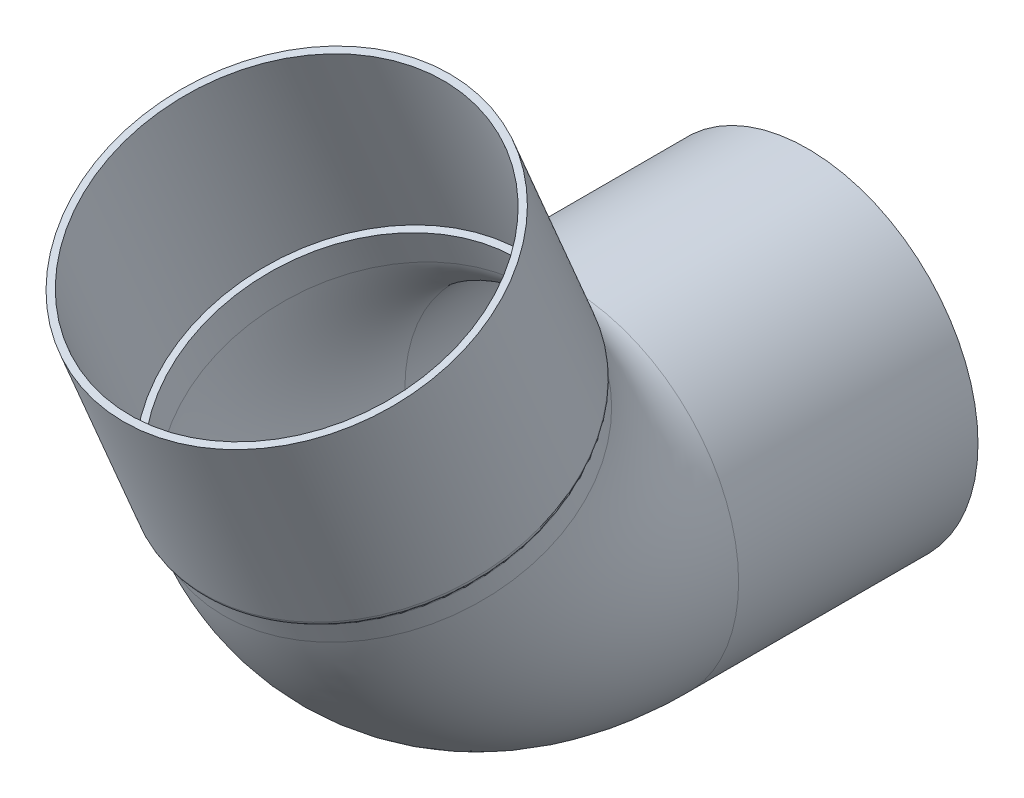
SolidWorks part; units mm, degrees
ref_plane "Plan de face" through (0, 0, 0) normal (0, 0, 1) x (1, 0, 0)
ref_plane "Plan de dessus" through (0, 0, 0) normal (0, 1, 0) x (1, 0, 0)
ref_plane "Plan de droite" through (0, 0, 0) normal (1, 0, 0) x (0, 0, -1)
sketch "Esquisse6" plane through (0, 0, 0) normal (0, 0, 1) x (1, 0, 0)
  circle A0 centre (0, 0) radius 25
sketch "Esquisse7" plane through (0, 0, 0) normal (1, 0, 0) x (0, 0, -1)
  line L0 (0, 0) -> (-35.1434, 0)
  line L1 (-62.7586, 18.2781) -> (-64.3775, 22.0921)
  arc A0 (-35.1434, 0) -> (-62.7586, 18.2781) centre (-35.1434, 30) cw
  point P6 (-55, 0)
  dimension "D4" = 30
  dimension "D1" = 24
  dimension "D2" = 55
  dimension "D3" = 67
sweep "Balayage-Mince2" add profiles "Esquisse6" path "Esquisse7" parameters "D1"=1
sketch "Esquisse8" plane through (0, 41.874, 17.7744) normal (0, 0.9205, 0.3907) x (1, 0, 0)
  line L0 (-24, -50.6278) -> (24, -50.6278) construction
  line L1 (0, -26.6278) -> (0, -74.6278) construction
  circle A0 centre (0, -50.6278) radius 24 construction
  circle A1 centre (0, -50.6278) radius 24 construction
  circle A2 centre (0, -50.6278) radius 24
  point P10 (0, -50.6278)
extrude "Extru.-Mince1" add sketch "Esquisse8" along normal blind 1 separate body thin contours A2 thin type one direction wall 2
sketch "Esquisse9" plane through (0, 42.7945, 18.1652) normal (0, 0.9205, 0.3907) x (1, 0, 0)
  line L0 (-24, -50.6278) -> (24, -50.6278) construction
  line L1 (0, -26.6278) -> (0, -74.6278) construction
  circle A0 centre (0, -50.6278) radius 24 construction
  circle A1 centre (0, -50.6278) radius 24 construction
  circle A2 centre (0, -50.6278) radius 26
extrude "Extru.-Mince2" add sketch "Esquisse9" along normal blind 30 thin thin type one direction reverse wall 1
fillet "Congé1" radius 1 1 edges at (25, 22.0921, 64.3775)
fillet "Congé2" radius 1 1 edges at (26, 22.0921, 64.3775)
